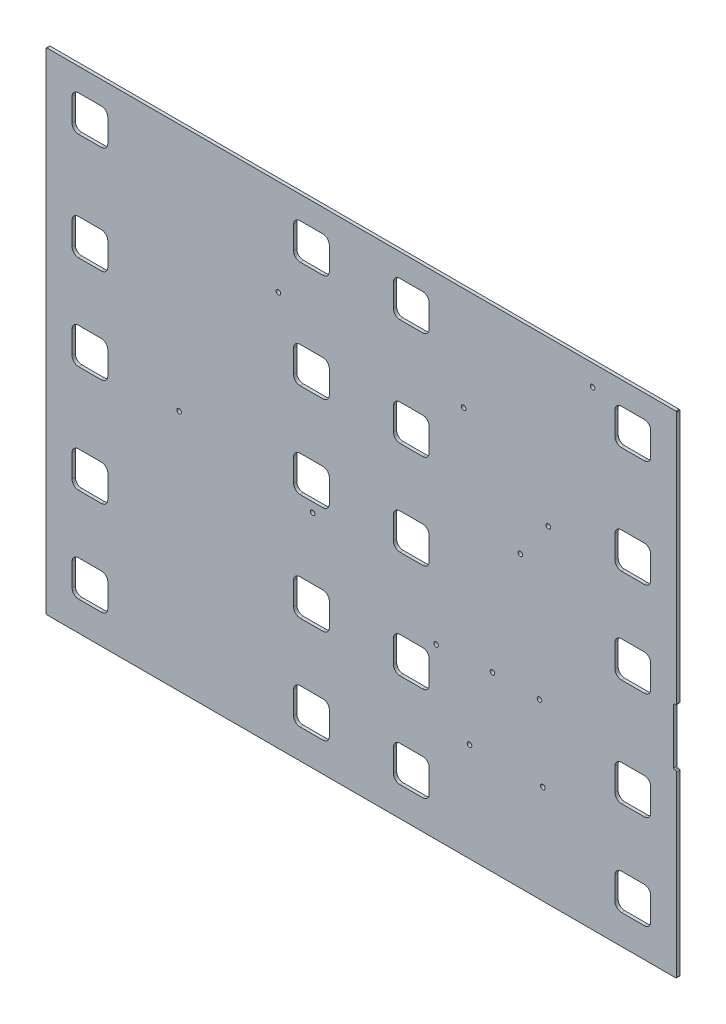
SolidWorks part; units mm, degrees
material "PP Film"
ref_plane "X-Y Datum" through (0, 0, 0) normal (0, 0, 1) x (1, 0, 0)
ref_plane "X-Z Datum" through (0, 0, 0) normal (0, 1, 0) x (1, 0, 0)
ref_plane "Y-Z Datum" through (0, 0, 0) normal (1, 0, 0) x (0, 0, -1)
sketch "Sketch9" plane through (0, 0, 0) normal (0, 0, 1) x (1, 0, 0)
  line L0 (-82.7559, -182.5893) -> (-82.7583, -160.1613) construction
  line L1 (-89.109, -153.8119) -> (-111.537, -153.8143) construction
  line L2 (-117.8863, -160.165) -> (-117.8839, -182.593) construction
  line L3 (-111.5333, -188.9423) -> (-89.1053, -188.9399) construction
  line L4 (475.4266, 171.7866) -> (-142.9187, 171.7216)
  line L12 (-111.5443, -83.8117) -> (-89.1163, -83.8093) construction
  line L13 (-82.767, -77.4587) -> (-82.7693, -55.0307) construction
  line L14 (-89.12, -48.6813) -> (-111.548, -48.6837) construction
  line L15 (-117.8973, -55.0344) -> (-117.895, -77.4624) construction
  line L16 (-82.7877, 120.2549) -> (-82.7901, 142.6829) construction
  line L17 (-89.1408, 149.0323) -> (-111.5688, 149.0299) construction
  line L18 (-117.9181, 142.6792) -> (-117.9157, 120.2512) construction
  line L19 (-111.5651, 113.9019) -> (-89.1371, 113.9043) construction
  line L20 (-111.554, 8.7713) -> (-89.126, 8.7737) construction
  line L21 (-117.9071, 37.5486) -> (-117.9047, 15.1206) construction
  line L22 (-89.1297, 43.9017) -> (-111.5577, 43.8993) construction
  line L23 (-82.7767, 15.1243) -> (-82.7791, 37.5523) construction
  line L24 (-82.7559, -182.5893) -> (-82.7583, -160.1613)
  line L25 (-89.109, -153.8119) -> (-111.537, -153.8143)
  line L26 (-117.8863, -160.165) -> (-117.8839, -182.593)
  line L27 (-111.5333, -188.9423) -> (-89.1053, -188.9399)
  line L28 (-111.5443, -83.8117) -> (-89.1163, -83.8093)
  line L29 (-82.767, -77.4587) -> (-82.7693, -55.0307)
  line L30 (-89.12, -48.6813) -> (-111.548, -48.6837)
  line L31 (-117.8973, -55.0344) -> (-117.895, -77.4624)
  line L32 (-82.7877, 120.2549) -> (-82.7901, 142.6829)
  line L33 (-89.1408, 149.0323) -> (-111.5688, 149.0299)
  line L34 (-117.9181, 142.6792) -> (-117.9157, 120.2512)
  line L35 (-111.5651, 113.9019) -> (-89.1371, 113.9043)
  line L36 (-111.554, 8.7713) -> (-89.126, 8.7737)
  line L37 (-117.9071, 37.5486) -> (-117.9047, 15.1206)
  line L38 (-89.1297, 43.9017) -> (-111.5577, 43.8993)
  line L39 (-82.7767, 15.1243) -> (-82.7791, 37.5523)
  line L40 (-82.7462, -275.1723) -> (-82.7486, -252.7443) construction
  line L41 (-89.0992, -246.3949) -> (-111.5272, -246.3973) construction
  line L42 (-117.8766, -252.748) -> (-117.8742, -275.176) construction
  line L43 (-111.5235, -281.5253) -> (-89.0955, -281.5229) construction
  line L44 (-82.7462, -275.1723) -> (-82.7486, -252.7443)
  line L45 (-89.0992, -246.3949) -> (-111.5272, -246.3973)
  line L46 (-117.8766, -252.748) -> (-117.8742, -275.176)
  line L47 (-111.5235, -281.5253) -> (-89.0955, -281.5229)
  line L174 (475.4266, 171.7866) -> (-142.9187, 171.7216)
  line L243 (-143.3593, 171.281) -> (-143.3088, -310.0568)
  line L244 (-143.3593, 171.281) -> (-143.3088, -310.0568)
  line L245 (-142.8681, -310.4974) -> (475.4773, -310.4324)
  line L246 (-142.8681, -310.4974) -> (475.4773, -310.4324)
  line L247 (475.9178, -309.9918) -> (475.8673, 171.346)
  line L248 (475.9178, -309.9918) -> (475.8673, 171.346)
  arc A0 (-89.1053, -188.9399) -> (-82.7559, -182.5893) centre (-89.1059, -182.5899) ccw construction
  arc A1 (-82.7583, -160.1613) -> (-89.109, -153.8119) centre (-89.1083, -160.1619) ccw construction
  arc A2 (-111.537, -153.8143) -> (-117.8863, -160.165) centre (-111.5363, -160.1643) ccw construction
  arc A3 (-117.8839, -182.593) -> (-111.5333, -188.9423) centre (-111.5339, -182.5923) ccw construction
  arc A4 (-89.1163, -83.8093) -> (-82.767, -77.4587) centre (-89.117, -77.4593) ccw construction
  arc A5 (-82.7693, -55.0307) -> (-89.12, -48.6813) centre (-89.1193, -55.0313) ccw construction
  arc A6 (-111.548, -48.6837) -> (-117.8973, -55.0344) centre (-111.5473, -55.0337) ccw construction
  arc A7 (-117.895, -77.4624) -> (-111.5443, -83.8117) centre (-111.545, -77.4617) ccw construction
  arc A8 (-89.1371, 113.9043) -> (-82.7877, 120.2549) centre (-89.1377, 120.2543) ccw construction
  arc A9 (-82.7901, 142.6829) -> (-89.1408, 149.0323) centre (-89.1401, 142.6823) ccw construction
  arc A10 (-111.5688, 149.0299) -> (-117.9181, 142.6792) centre (-111.5681, 142.6799) ccw construction
  arc A11 (-117.9157, 120.2512) -> (-111.5651, 113.9019) centre (-111.5657, 120.2519) ccw construction
  arc A12 (-82.7791, 37.5523) -> (-89.1297, 43.9017) centre (-89.1291, 37.5517) ccw construction
  arc A13 (-89.126, 8.7737) -> (-82.7767, 15.1243) centre (-89.1267, 15.1237) ccw construction
  arc A14 (-117.9047, 15.1206) -> (-111.554, 8.7713) centre (-111.5547, 15.1213) ccw construction
  arc A15 (-111.5577, 43.8993) -> (-117.9071, 37.5486) centre (-111.5571, 37.5493) ccw construction
  arc A16 (-89.1053, -188.9399) -> (-82.7559, -182.5893) centre (-89.1059, -182.5899) ccw
  arc A17 (-82.7583, -160.1613) -> (-89.109, -153.8119) centre (-89.1083, -160.1619) ccw
  arc A18 (-111.537, -153.8143) -> (-117.8863, -160.165) centre (-111.5363, -160.1643) ccw
  arc A19 (-117.8839, -182.593) -> (-111.5333, -188.9423) centre (-111.5339, -182.5923) ccw
  arc A20 (-89.1163, -83.8093) -> (-82.767, -77.4587) centre (-89.117, -77.4593) ccw
  arc A21 (-82.7693, -55.0307) -> (-89.12, -48.6813) centre (-89.1193, -55.0313) ccw
  arc A22 (-111.548, -48.6837) -> (-117.8973, -55.0344) centre (-111.5473, -55.0337) ccw
  arc A23 (-117.895, -77.4624) -> (-111.5443, -83.8117) centre (-111.545, -77.4617) ccw
  arc A24 (-89.1371, 113.9043) -> (-82.7877, 120.2549) centre (-89.1377, 120.2543) ccw
  arc A25 (-82.7901, 142.6829) -> (-89.1408, 149.0323) centre (-89.1401, 142.6823) ccw
  arc A26 (-111.5688, 149.0299) -> (-117.9181, 142.6792) centre (-111.5681, 142.6799) ccw
  arc A27 (-117.9157, 120.2512) -> (-111.5651, 113.9019) centre (-111.5657, 120.2519) ccw
  arc A28 (-82.7791, 37.5523) -> (-89.1297, 43.9017) centre (-89.1291, 37.5517) ccw
  arc A29 (-89.126, 8.7737) -> (-82.7767, 15.1243) centre (-89.1267, 15.1237) ccw
  arc A30 (-117.9047, 15.1206) -> (-111.554, 8.7713) centre (-111.5547, 15.1213) ccw
  arc A31 (-111.5577, 43.8993) -> (-117.9071, 37.5486) centre (-111.5571, 37.5493) ccw
  arc A32 (-89.0955, -281.5229) -> (-82.7462, -275.1723) centre (-89.0962, -275.1729) ccw construction
  arc A33 (-111.5272, -246.3973) -> (-117.8766, -252.748) centre (-111.5266, -252.7473) ccw construction
  arc A34 (-117.8742, -275.176) -> (-111.5235, -281.5253) centre (-111.5242, -275.1753) ccw construction
  arc A35 (-89.0955, -281.5229) -> (-82.7462, -275.1723) centre (-89.0962, -275.1729) ccw
  arc A36 (-111.5272, -246.3973) -> (-117.8766, -252.748) centre (-111.5266, -252.7473) ccw
  arc A37 (-117.8742, -275.176) -> (-111.5235, -281.5253) centre (-111.5242, -275.1753) ccw
  arc A38 (-82.7486, -252.7443) -> (-89.0992, -246.3949) centre (-89.0986, -252.7449) ccw construction
  arc A39 (-82.7486, -252.7443) -> (-89.0992, -246.3949) centre (-89.0986, -252.7449) ccw
  arc A72 (-142.8681, -310.4974) -> (-143.3088, -310.0568) centre (-144.189, -311.3779) ccw
  arc A108 (-142.8681, -310.4974) -> (-143.3088, -310.0568) centre (-144.189, -311.3779) ccw
  arc A128 (475.9178, -309.9918) -> (475.4773, -310.4324) centre (476.7984, -311.3127) ccw
  arc A132 (475.9178, -309.9918) -> (475.4773, -310.4324) centre (476.7984, -311.3127) ccw
  arc A136 (475.4266, 171.7866) -> (475.8673, 171.346) centre (476.7475, 172.6671) ccw
  arc A140 (475.4266, 171.7866) -> (475.8673, 171.346) centre (476.7475, 172.6671) ccw
  arc A142 (-143.3593, 171.281) -> (-142.9187, 171.7216) centre (-144.2398, 172.6019) ccw
  arc A144 (-143.3593, 171.281) -> (-142.9187, 171.7216) centre (-144.2398, 172.6019) ccw
  dimension "D1" = 0
extrude "Boss-Extrude2" add sketch "Sketch9" along normal blind 3.175 contours L244 L246 L174 A39 L44 A35 L47 A37 L46 A36 L45 A31 L38 A28 L39 A29 L36 A30 L37 A27 L34 A26 L33 A25 L32 A24 L35 A23 L31 A22 L30 A21 L29 A20 L28 A19 L26 A18 L25 A17 L24 A16 L27 | L44 A39 L45 A36 L46 A37 L47 A35 | L26 A19 L27 A16 L24 A17 L25 A18 | L38 A31 L37 A30 L36 A29 L39 A28 | L34 A27 L35 A24 L32 A25 L33 A26 | L31 A23 L28 A20 L29 A21 L30 A22 region at (171.7433, -69.3677, 0) region at (-100.3211, -171.3771, 0) region at (-100.3322, -66.2465, 0) region at (-100.3529, 131.4671, 0) region at (-100.3419, 26.3365, 0) region at (-100.3114, -263.9601, 0)
sketch "Sketch10" plane through (0, 0, 3.175) normal (0, 0, 1) x (1, 0, 0)
  line L9 (476.8831, 172.8027) -> (-144.3755, 172.7375)
  line L10 (-144.3755, 172.7375) -> (-144.3246, -311.5135)
  line L11 (-144.3246, -311.5135) -> (476.934, -311.4483)
  line L12 (-117.8863, -160.165) -> (-117.8839, -182.593)
  line L13 (-111.5333, -188.9423) -> (-89.1053, -188.9399)
  line L14 (-82.7559, -182.5893) -> (-82.7583, -160.1613)
  line L15 (-89.109, -153.8119) -> (-111.537, -153.8143)
  line L16 (-117.8863, -160.165) -> (-117.8839, -182.593)
  line L17 (-111.5333, -188.9423) -> (-89.1053, -188.9399)
  line L18 (-82.7559, -182.5893) -> (-82.7583, -160.1613)
  line L19 (-89.109, -153.8119) -> (-111.537, -153.8143)
  line L20 (-117.8766, -252.748) -> (-117.8742, -275.176)
  line L21 (-89.0992, -246.3949) -> (-111.5272, -246.3973)
  line L22 (-82.7462, -275.1723) -> (-82.7486, -252.7443)
  line L23 (-111.5235, -281.5253) -> (-89.0955, -281.5229)
  line L24 (-117.8766, -252.748) -> (-117.8742, -275.176)
  line L25 (-89.0992, -246.3949) -> (-111.5272, -246.3973)
  line L26 (-82.7462, -275.1723) -> (-82.7486, -252.7443)
  line L27 (-111.5235, -281.5253) -> (-89.0955, -281.5229)
  line L28 (-89.12, -48.6813) -> (-111.548, -48.6837)
  line L29 (-117.8973, -55.0344) -> (-117.895, -77.4624)
  line L30 (-111.5443, -83.8117) -> (-89.1163, -83.8093)
  line L31 (-82.767, -77.4587) -> (-82.7693, -55.0307)
  line L32 (-89.12, -48.6813) -> (-111.548, -48.6837)
  line L33 (-117.8973, -55.0344) -> (-117.895, -77.4624)
  line L34 (-111.5443, -83.8117) -> (-89.1163, -83.8093)
  line L35 (-82.767, -77.4587) -> (-82.7693, -55.0307)
  line L36 (-82.7877, 120.2549) -> (-82.7901, 142.6829)
  line L37 (-111.5651, 113.9019) -> (-89.1371, 113.9043)
  line L38 (-117.9181, 142.6792) -> (-117.9157, 120.2512)
  line L39 (-89.1408, 149.0323) -> (-111.5688, 149.0299)
  line L40 (-82.7877, 120.2549) -> (-82.7901, 142.6829)
  line L41 (-111.5651, 113.9019) -> (-89.1371, 113.9043)
  line L42 (-117.9181, 142.6792) -> (-117.9157, 120.2512)
  line L43 (-89.1408, 149.0323) -> (-111.5688, 149.0299)
  line L44 (-111.554, 8.7713) -> (-89.126, 8.7737)
  line L45 (-82.7767, 15.1243) -> (-82.7791, 37.5523)
  line L46 (-89.1297, 43.9017) -> (-111.5577, 43.8993)
  line L47 (-117.9071, 37.5486) -> (-117.9047, 15.1206)
  line L48 (-111.554, 8.7713) -> (-89.126, 8.7737)
  line L49 (-82.7767, 15.1243) -> (-82.7791, 37.5523)
  line L50 (-89.1297, 43.9017) -> (-111.5577, 43.8993)
  line L51 (-117.9071, 37.5486) -> (-117.9047, 15.1206)
  line L53 (476.934, -311.4483) -> (476.8831, 172.8027)
  arc A4 (-117.8839, -182.593) -> (-111.5333, -188.9423) centre (-111.5339, -182.5923) ccw
  arc A5 (-89.1053, -188.9399) -> (-82.7559, -182.5893) centre (-89.1059, -182.5899) ccw
  arc A6 (-82.7583, -160.1613) -> (-89.109, -153.8119) centre (-89.1083, -160.1619) ccw
  arc A7 (-111.537, -153.8143) -> (-117.8863, -160.165) centre (-111.5363, -160.1643) ccw
  arc A8 (-117.8839, -182.593) -> (-111.5333, -188.9423) centre (-111.5339, -182.5923) ccw
  arc A9 (-89.1053, -188.9399) -> (-82.7559, -182.5893) centre (-89.1059, -182.5899) ccw
  arc A10 (-82.7583, -160.1613) -> (-89.109, -153.8119) centre (-89.1083, -160.1619) ccw
  arc A11 (-111.537, -153.8143) -> (-117.8863, -160.165) centre (-111.5363, -160.1643) ccw
  arc A12 (-111.5272, -246.3973) -> (-117.8766, -252.748) centre (-111.5266, -252.7473) ccw
  arc A13 (-82.7486, -252.7443) -> (-89.0992, -246.3949) centre (-89.0986, -252.7449) ccw
  arc A14 (-89.0955, -281.5229) -> (-82.7462, -275.1723) centre (-89.0962, -275.1729) ccw
  arc A15 (-117.8742, -275.176) -> (-111.5235, -281.5253) centre (-111.5242, -275.1753) ccw
  arc A16 (-111.5272, -246.3973) -> (-117.8766, -252.748) centre (-111.5266, -252.7473) ccw
  arc A17 (-82.7486, -252.7443) -> (-89.0992, -246.3949) centre (-89.0986, -252.7449) ccw
  arc A18 (-89.0955, -281.5229) -> (-82.7462, -275.1723) centre (-89.0962, -275.1729) ccw
  arc A19 (-117.8742, -275.176) -> (-111.5235, -281.5253) centre (-111.5242, -275.1753) ccw
  arc A20 (-111.548, -48.6837) -> (-117.8973, -55.0344) centre (-111.5473, -55.0337) ccw
  arc A21 (-117.895, -77.4624) -> (-111.5443, -83.8117) centre (-111.545, -77.4617) ccw
  arc A22 (-89.1163, -83.8093) -> (-82.767, -77.4587) centre (-89.117, -77.4593) ccw
  arc A23 (-82.7693, -55.0307) -> (-89.12, -48.6813) centre (-89.1193, -55.0313) ccw
  arc A24 (-111.548, -48.6837) -> (-117.8973, -55.0344) centre (-111.5473, -55.0337) ccw
  arc A25 (-117.895, -77.4624) -> (-111.5443, -83.8117) centre (-111.545, -77.4617) ccw
  arc A26 (-89.1163, -83.8093) -> (-82.767, -77.4587) centre (-89.117, -77.4593) ccw
  arc A27 (-82.7693, -55.0307) -> (-89.12, -48.6813) centre (-89.1193, -55.0313) ccw
  arc A28 (-89.1371, 113.9043) -> (-82.7877, 120.2549) centre (-89.1377, 120.2543) ccw
  arc A29 (-117.9157, 120.2512) -> (-111.5651, 113.9019) centre (-111.5657, 120.2519) ccw
  arc A30 (-111.5688, 149.0299) -> (-117.9181, 142.6792) centre (-111.5681, 142.6799) ccw
  arc A31 (-82.7901, 142.6829) -> (-89.1408, 149.0323) centre (-89.1401, 142.6823) ccw
  arc A32 (-89.1371, 113.9043) -> (-82.7877, 120.2549) centre (-89.1377, 120.2543) ccw
  arc A33 (-117.9157, 120.2512) -> (-111.5651, 113.9019) centre (-111.5657, 120.2519) ccw
  arc A34 (-111.5688, 149.0299) -> (-117.9181, 142.6792) centre (-111.5681, 142.6799) ccw
  arc A35 (-82.7901, 142.6829) -> (-89.1408, 149.0323) centre (-89.1401, 142.6823) ccw
  arc A36 (-89.126, 8.7737) -> (-82.7767, 15.1243) centre (-89.1267, 15.1237) ccw
  arc A37 (-82.7791, 37.5523) -> (-89.1297, 43.9017) centre (-89.1291, 37.5517) ccw
  arc A38 (-111.5577, 43.8993) -> (-117.9071, 37.5486) centre (-111.5571, 37.5493) ccw
  arc A39 (-117.9047, 15.1206) -> (-111.554, 8.7713) centre (-111.5547, 15.1213) ccw
  arc A40 (-89.126, 8.7737) -> (-82.7767, 15.1243) centre (-89.1267, 15.1237) ccw
  arc A41 (-82.7791, 37.5523) -> (-89.1297, 43.9017) centre (-89.1291, 37.5517) ccw
  arc A42 (-111.5577, 43.8993) -> (-117.9071, 37.5486) centre (-111.5571, 37.5493) ccw
  arc A43 (-117.9047, 15.1206) -> (-111.554, 8.7713) centre (-111.5547, 15.1213) ccw
  dimension "D2" = 0
  dimension "D3" = 0
  dimension "D4" = 0
  dimension "D5" = 0
  dimension "D6" = 0
extrude "Cut-Extrude6" cut sketch "Sketch10" against normal through all contours L40 A35 L43 A34 L42 A33 L41 A32 | L51 A43 L48 A40 L49 A41 L50 A42 | L35 A27 L32 A24 L33 A25 L34 A26 | L19 A11 L16 A8 L17 A9 L18 A10 | L24 A19 L27 A18 L26 A17 L25 A16 region at (-100.3211, -171.3771, 3.175) region at (-100.3114, -263.9601, 3.175) region at (-100.3322, -66.2465, 3.175) region at (-100.3529, 131.4671, 3.175) region at (-100.3419, 26.3365, 3.175)
pattern_linear "LPattern2" count 2 spacing 217.5764 along (1, 0.0001, 0) of "Cut-Extrude6"
ref_plane "Plane1" through (166.272, 0.0175, 0) normal (-1, -0.0001, 0) x (0, 0, 1)
mirror "Mirror1" about plane through (166.272, 0.0175, 0) normal (-1, -0.0001, 0) of "LPattern2", "Cut-Extrude6"
sketch "Sketch11" plane through (0, 0, 3.175) normal (0, 0, 1) x (1, 0, 0)
  circle A3 centre (295.0226, -140.5889) radius 1.5875
  circle A5 centre (295.0226, -140.5889) radius 1.5875
  circle A7 centre (393.3194, 151.1404) radius 1.5875
  circle A9 centre (393.3194, 151.1404) radius 1.5875
  circle A11 centre (266.6754, 70.3421) radius 1.5875
  circle A13 centre (266.6754, 70.3421) radius 1.5875
  circle A15 centre (84.813, 77.608) radius 1.5875
  circle A17 centre (84.813, 77.608) radius 1.5875
  circle A19 centre (-12.7212, -72.4022) radius 1.5875
  circle A21 centre (-12.7212, -72.4022) radius 1.5875
  circle A23 centre (349.9236, 11.0749) radius 1.5875
  circle A44 centre (349.9236, 11.0749) radius 1.5875
  circle A45 centre (322.4275, -26.052) radius 1.5875
  circle A46 centre (322.4275, -26.052) radius 1.5875
  circle A47 centre (341.2226, -140.584) radius 1.5875
  circle A48 centre (341.2226, -140.584) radius 1.5875
  circle A49 centre (344.4952, -213.3337) radius 1.5875
  circle A50 centre (344.4952, -213.3337) radius 1.5875
  circle A51 centre (118.3901, -93.0713) radius 1.5875
  circle A52 centre (118.3901, -93.0713) radius 1.5875
  circle A53 centre (239.6805, -144.4936) radius 1.5875
  circle A54 centre (239.6805, -144.4936) radius 1.5875
  circle A55 centre (272.4952, -213.3413) radius 1.5875
  circle A56 centre (272.4952, -213.3413) radius 1.5875
  dimension "D1" = 0
  dimension "D2" = 0
  dimension "D3" = 0
  dimension "D4" = 0
  dimension "D5" = 0
  dimension "D6" = 0
  dimension "D7" = 0
  dimension "D8" = 0
  dimension "D9" = 0
  dimension "D10" = 0
  dimension "D11" = 0
  dimension "D12" = 0
sketch "Sketch12" plane through (0, 0, 3.175) normal (0, 0, 1) x (1, 0, 0)
  line L0 (472.9633, -129.0942) -> (472.9585, -83.0942)
  line L1 (472.9632, -127.919) -> (472.9635, -130.2694) construction
  line L2 (472.9584, -81.919) -> (472.9586, -84.2694) construction
  line L3 (475.9178, -309.9918) -> (475.8673, 171.346) construction
  line L4 (472.9609, -78.1542) -> (472.9609, -134.0342)
  line L5 (472.9609, -134.0342) -> (475.8994, -134.0342)
  line L6 (472.9609, -78.1542) -> (475.8935, -78.1542)
  line L9 (475.9178, -309.9918) -> (475.8673, 171.346)
  point P11 (472.9609, -106.0942)
  dimension "D1" = 46
  dimension "D2" = 55.88
extrude "Cut-Extrude8" cut sketch "Sketch12" against normal through all contours L9 region at (474.4287, -106.1035, 3.175)
hole_wizard "M4 Clearance Hole1" positions "Sketch13" profile "Sketch14" hole size "M4" standard "ANSI Metric" end condition through all
sketch "Sketch13" plane through (0, 0, 3.175) normal (0, 0, 1) x (1, 0, 0)
  point P0 (-12.7212, -72.4022)
  point P3 (118.3901, -93.0713)
  point P6 (272.4952, -213.3413)
  point P9 (344.4952, -213.3337)
  point P12 (239.6805, -144.4936)
  point P15 (295.0226, -140.5889)
  point P18 (341.2226, -140.584)
  point P21 (322.4275, -26.052)
  point P24 (349.9236, 11.0749)
  point P27 (266.6754, 70.3421)
  point P30 (393.3194, 151.1404)
  point P33 (84.813, 77.608)
sketch "Sketch14" plane through (-12.7212, -72.4022, 3.175) normal (1, 0, 0) x (0, -1, 0)
  line L0 (0, 0) -> (0, 3.175)
  line L1 (0, 3.175) -> (2.25, 3.175)
  line L2 (2.25, 3.175) -> (2.25, 0)
  line L5 (2.25, 0) -> (0, 0)
  line L11 (0, -6.35) -> (0, 107.95) construction
  dimension "Thru Hole Dia." = 4.5
  dimension "Thru Hole Depth" = 3.175
fillet "Fillet2" radius 0.7937 8 edges at (-142.8681, -310.4974, 1.5875) (-143.3088, -310.0568, 1.5875) (475.4773, -310.4324, 1.5875) (475.9178, -309.9918, 1.5875) (475.8673, 171.346, 1.5875) (475.4266, 171.7866, 1.5875) (-142.9187, 171.7216, 1.5875) (-143.3593, 171.281, 1.5875)
fillet "Fillet3" radius 1.016 4 edges at (475.8935, -78.1542, 1.5875) (472.9609, -78.1542, 1.5875) (475.8994, -134.0342, 1.5875) (472.9609, -134.0342, 1.5875)
